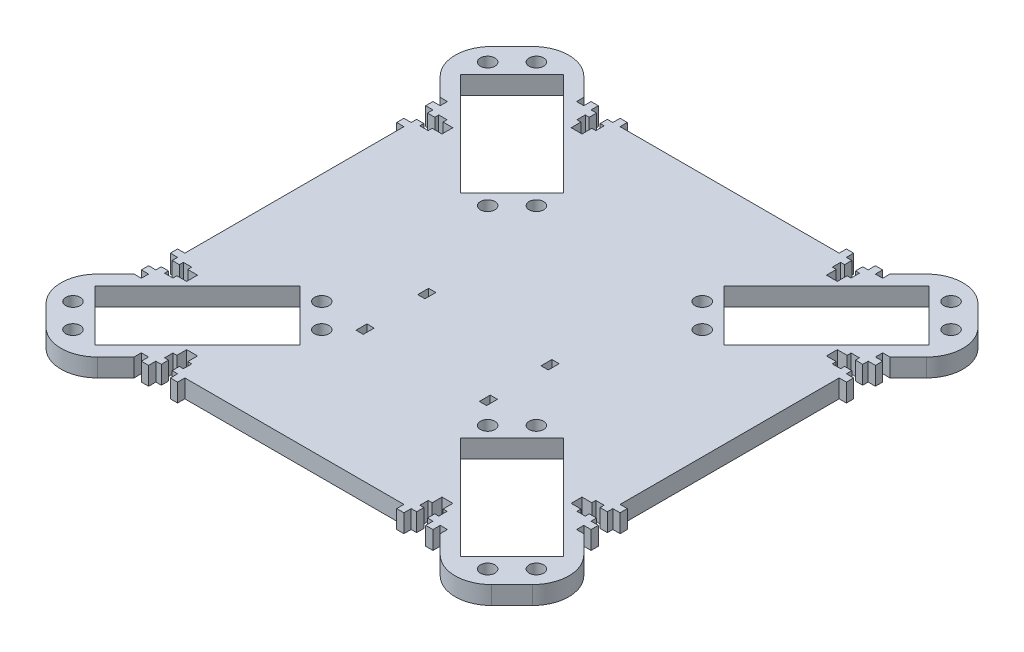
SolidWorks part; units mm, degrees
ref_plane "Front Plane" through (0, 0, 0) normal (0, 0, 1) x (1, 0, 0)
ref_plane "Top Plane" through (0, 0, 0) normal (0, 1, 0) x (1, 0, 0)
ref_plane "Right Plane" through (0, 0, 0) normal (1, 0, 0) x (0, 0, -1)
sketch "Sketch1" plane through (0, 0, 0) normal (0, 1, 0) x (1, 0, 0)
  line L1 (0, 0) -> (120, 0)
  line L2 (0, 0) -> (0, 120)
  line L3 (0, 120) -> (120, 120)
  line L4 (120, 0) -> (120, 120)
  dimension "D1" = 120
  dimension "D2" = 120
extrude "Boss-Extrude1" add sketch "Sketch1" along normal blind 5
sketch "Sketch2" plane through (0, 5, 0) normal (0, 1, 0) x (1, 0, 0)
  line L0 (60, 120) -> (60, 0) construction
  line L1 (120, 120) -> (0, 120) construction
  line L2 (0, 0) -> (120, 0) construction
  line L3 (120, 60) -> (0, 60) construction
  line L4 (120, 0) -> (120, 120) construction
  line L5 (0, 120) -> (0, 0) construction
  line L6 (60, 60) -> (120, 120) construction
  line L7 (110.1005, 110.1005) -> (120, 100.201) construction
  line L8 (110.1005, 110.1005) -> (100.201, 120) construction
  line L9 (100.201, 120) -> (120, 100.201)
  line L10 (100.201, 120) -> (114.3431, 134.1421)
  line L11 (120, 100.201) -> (134.1421, 114.3431)
  line L12 (114.3431, 134.1421) -> (134.1421, 114.3431)
  line L13 (0, 100.201) -> (-14.1421, 114.3431)
  line L14 (5.6569, 134.1421) -> (-14.1421, 114.3431)
  line L15 (19.799, 120) -> (5.6569, 134.1421)
  line L16 (19.799, 120) -> (0, 100.201)
  line L17 (19.799, 0) -> (0, 19.799)
  line L18 (19.799, 0) -> (5.6569, -14.1421)
  line L19 (5.6569, -14.1421) -> (-14.1421, 5.6569)
  line L20 (0, 19.799) -> (-14.1421, 5.6569)
  line L21 (120, 19.799) -> (134.1421, 5.6569)
  line L22 (114.3431, -14.1421) -> (134.1421, 5.6569)
  line L23 (100.201, 0) -> (114.3431, -14.1421)
  line L24 (100.201, 0) -> (120, 19.799)
  point P33 (120, 100.201)
  point P34 (100.201, 120)
  dimension "D1" = 28
  dimension "D2" = 20
extrude "Boss-Extrude3" add sketch "Sketch2" against normal blind 5
sketch "Sketch3" plane through (0, 5, 0) normal (0, 1, 0) x (1, 0, 0)
  line L0 (-4.2426, -4.2426) -> (124.2426, 124.2426) construction
  line L1 (-14.1421, 5.6569) -> (5.6569, -14.1421) construction
  line L2 (134.1421, 114.3431) -> (114.3431, 134.1421) construction
  line L3 (0, 19.799) -> (19.799, 0) construction
  line L4 (2.4819, 2.4819) -> (12.3814, -7.4176) construction
  line L5 (5.6569, -14.1421) -> (19.799, 0) construction
  line L6 (30.7662, 30.7662) -> (43.5292, 18.0033) construction
  line L7 (9.553, -4.5891) -> (37.8373, 23.6951)
  line L8 (9.553, -4.5891) -> (-4.5891, 9.553)
  line L9 (37.8373, 23.6951) -> (23.6951, 37.8373)
  line L10 (-4.5891, 9.553) -> (23.6951, 37.8373)
  line L11 (-0.5233, -0.5233) -> (6.5401, -7.5867) construction
  line L12 (23.6951, 9.553) -> (9.553, 23.6951) construction
  line L13 (0, 60) -> (120, 60) construction
  line L14 (0, 100.201) -> (0, 19.799) construction
  line L15 (120, 19.799) -> (120, 100.201) construction
  line L16 (60, 0) -> (60, 120) construction
  line L17 (19.799, 0) -> (100.201, 0) construction
  line L18 (100.201, 120) -> (19.799, 120) construction
  line L19 (82.1627, 23.6951) -> (96.3049, 37.8373)
  line L20 (124.5891, 9.553) -> (96.3049, 37.8373)
  line L21 (110.447, -4.5891) -> (124.5891, 9.553)
  line L22 (110.447, -4.5891) -> (82.1627, 23.6951)
  line L23 (110.447, 124.5891) -> (82.1627, 96.3049)
  line L24 (110.447, 124.5891) -> (124.5891, 110.447)
  line L25 (124.5891, 110.447) -> (96.3049, 82.1627)
  line L26 (82.1627, 96.3049) -> (96.3049, 82.1627)
  line L27 (37.8373, 96.3049) -> (23.6951, 82.1627)
  line L28 (-4.5891, 110.447) -> (23.6951, 82.1627)
  line L29 (9.553, 124.5891) -> (-4.5891, 110.447)
  line L30 (9.553, 124.5891) -> (37.8373, 96.3049)
  circle A0 centre (2.8355, -3.882) radius 2
  circle A1 centre (-3.882, 2.8355) radius 2
  circle A2 centre (37.1302, 30.4127) radius 2
  circle A3 centre (30.4127, 37.1302) radius 2
  circle A4 centre (117.1645, -3.882) radius 2
  circle A5 centre (123.882, 2.8355) radius 2
  circle A6 centre (82.8698, 30.4127) radius 2
  circle A7 centre (89.5873, 37.1302) radius 2
  circle A8 centre (117.1645, 123.882) radius 2
  circle A9 centre (123.882, 117.1645) radius 2
  circle A10 centre (82.8698, 89.5873) radius 2
  circle A11 centre (89.5873, 82.8698) radius 2
  circle A12 centre (2.8355, 123.882) radius 2
  circle A13 centre (-3.882, 117.1645) radius 2
  circle A14 centre (37.1302, 89.5873) radius 2
  circle A15 centre (30.4127, 82.8698) radius 2
  point P10 (9.8995, 9.8995)
  point P11 (30.7662, 30.7662)
  point P13 (2.4819, 2.4819)
  dimension "D5" = 4
  dimension "D6" = 9.5
  dimension "D7" = 4.25
  dimension "D1" = 29.51
  dimension "D2" = 10.49
  dimension "D3" = 20
  dimension "D4" = 4.25
extrude "Cut-Extrude1" cut sketch "Sketch3" against normal blind 5
sketch "Sketch6" plane through (0, 5, 0) normal (0, 1, 0) x (1, 0, 0)
  line L0 (0, 19.799) -> (0, 17.799)
  line L1 (0, 17.799) -> (-2, 17.799)
  line L2 (0, 19.799) -> (-14.1421, 5.6569) construction
  line L3 (-2, 17.799) -> (0, 19.799)
  line L4 (0, 0) -> (124.2426, 124.2426) construction
  line L5 (134.1421, 114.3431) -> (114.3431, 134.1421) construction
  line L6 (60, 120) -> (60, 0) construction
  line L7 (100.201, 120) -> (19.799, 120) construction
  line L8 (19.799, 0) -> (100.201, 0) construction
  line L9 (0, 60) -> (120, 60) construction
  line L10 (0, 100.201) -> (0, 19.799) construction
  line L11 (120, 19.799) -> (120, 100.201) construction
  line L12 (17.799, -2) -> (19.799, 0)
  line L13 (17.799, 0) -> (17.799, -2)
  line L14 (19.799, 0) -> (17.799, 0)
  line L15 (100.201, 0) -> (102.201, 0)
  line L16 (102.201, 0) -> (102.201, -2)
  line L17 (102.201, -2) -> (100.201, 0)
  line L18 (122, 17.799) -> (120, 19.799)
  line L19 (120, 17.799) -> (122, 17.799)
  line L20 (120, 19.799) -> (120, 17.799)
  line L21 (120, 100.201) -> (120, 102.201)
  line L22 (120, 102.201) -> (122, 102.201)
  line L23 (122, 102.201) -> (120, 100.201)
  line L24 (102.201, 122) -> (100.201, 120)
  line L25 (102.201, 120) -> (102.201, 122)
  line L26 (100.201, 120) -> (102.201, 120)
  line L27 (19.799, 120) -> (17.799, 120)
  line L28 (17.799, 120) -> (17.799, 122)
  line L29 (17.799, 122) -> (19.799, 120)
  line L30 (-2, 102.201) -> (0, 100.201)
  line L31 (0, 102.201) -> (-2, 102.201)
  line L32 (0, 100.201) -> (0, 102.201)
  dimension "D1" = 2
extrude "Cut-Extrude4" cut sketch "Sketch6" against normal blind 10
fillet "Fillet1" radius 10 8 edges at (5.6569, 2.5, 14.1421) (-14.1421, 2.5, -5.6569) (-14.1421, 2.5, -114.3431) (5.6569, 2.5, -134.1421) (114.3431, 2.5, -134.1421) (134.1421, 2.5, -114.3431) (134.1421, 2.5, -5.6569) (114.3431, 2.5, 14.1421)
sketch "Sketch8" plane through (0, 5, 0) normal (0, 1, 0) x (1, 0, 0)
  line L0 (60, 0) -> (60, 120) construction
  line L1 (17.799, 0) -> (102.201, 0) construction
  line L2 (102.201, 120) -> (17.799, 120) construction
  line L3 (0, 60) -> (120, 60) construction
  line L4 (0, 102.201) -> (0, 17.799) construction
  line L5 (120, 17.799) -> (120, 102.201) construction
  line L6 (-4.2426, 124.2426) -> (124.2426, -4.2426) construction
  line L7 (-1.4142, 127.0711) -> (-7.0711, 121.4142) construction
  line L8 (121.4142, -7.0711) -> (127.0711, -1.4142) construction
  line L9 (24.799, 0) -> (24.799, 7) construction
  line L10 (23.299, 2) -> (23.299, 0)
  line L11 (26.299, 7) -> (23.299, 7)
  line L12 (26.299, 7) -> (26.299, 4.3)
  line L13 (26.299, 0) -> (23.299, 0)
  line L14 (23.299, 7) -> (23.299, 4.3)
  line L15 (26.299, 7) -> (23.299, 0) construction
  line L16 (26.299, 0) -> (23.299, 7) construction
  line L17 (23.299, 2) -> (22.199, 2)
  line L19 (23.299, 4.3) -> (22.199, 4.3)
  line L20 (22.199, 2) -> (22.199, 4.3)
  line L21 (26.299, 4.3) -> (27.399, 4.3)
  line L22 (27.399, 2) -> (27.399, 4.3)
  line L23 (26.299, 2) -> (27.399, 2)
  line L24 (26.299, 2) -> (26.299, 0)
  line L25 (17.799, 0) -> (17.799, -2) construction
  line L26 (93.701, 0) -> (96.701, 7) construction
  line L27 (93.701, 7) -> (96.701, 0) construction
  line L28 (95.201, 0) -> (95.201, 7) construction
  line L29 (93.701, 2) -> (93.701, 0)
  line L30 (93.701, 2) -> (92.601, 2)
  line L31 (92.601, 2) -> (92.601, 4.3)
  line L32 (93.701, 4.3) -> (92.601, 4.3)
  line L33 (97.801, 2) -> (97.801, 4.3)
  line L34 (96.701, 4.3) -> (97.801, 4.3)
  line L35 (96.701, 2) -> (97.801, 2)
  line L36 (96.701, 7) -> (96.701, 4.3)
  line L37 (93.701, 0) -> (96.701, 0)
  line L38 (93.701, 7) -> (93.701, 4.3)
  line L39 (93.701, 7) -> (96.701, 7)
  line L40 (96.701, 2) -> (96.701, 0)
  line L41 (95.201, 120) -> (95.201, 113) construction
  line L42 (93.701, 113) -> (96.701, 120) construction
  line L43 (93.701, 120) -> (96.701, 113) construction
  line L44 (26.299, 120) -> (23.299, 113) construction
  line L45 (26.299, 113) -> (23.299, 120) construction
  line L46 (24.799, 120) -> (24.799, 113) construction
  line L47 (96.701, 118) -> (96.701, 120)
  line L48 (93.701, 113) -> (96.701, 113)
  line L49 (93.701, 113) -> (93.701, 115.7)
  line L50 (93.701, 120) -> (96.701, 120)
  line L51 (96.701, 113) -> (96.701, 115.7)
  line L52 (96.701, 118) -> (97.801, 118)
  line L53 (96.701, 115.7) -> (97.801, 115.7)
  line L54 (97.801, 118) -> (97.801, 115.7)
  line L55 (93.701, 115.7) -> (92.601, 115.7)
  line L56 (92.601, 118) -> (92.601, 115.7)
  line L57 (93.701, 118) -> (92.601, 118)
  line L58 (93.701, 118) -> (93.701, 120)
  line L59 (26.299, 118) -> (26.299, 120)
  line L60 (26.299, 118) -> (27.399, 118)
  line L61 (27.399, 118) -> (27.399, 115.7)
  line L62 (26.299, 115.7) -> (27.399, 115.7)
  line L63 (22.199, 118) -> (22.199, 115.7)
  line L64 (23.299, 115.7) -> (22.199, 115.7)
  line L65 (23.299, 118) -> (22.199, 118)
  line L66 (23.299, 113) -> (23.299, 115.7)
  line L67 (26.299, 120) -> (23.299, 120)
  line L68 (26.299, 113) -> (26.299, 115.7)
  line L69 (26.299, 113) -> (23.299, 113)
  line L70 (23.299, 118) -> (23.299, 120)
  line L71 (0, 95.201) -> (7, 95.201) construction
  line L72 (7, 93.701) -> (0, 96.701) construction
  line L73 (0, 93.701) -> (7, 96.701) construction
  line L74 (0, 26.299) -> (7, 23.299) construction
  line L75 (7, 26.299) -> (0, 23.299) construction
  line L76 (0, 24.799) -> (7, 24.799) construction
  line L77 (120, 24.799) -> (113, 24.799) construction
  line L78 (113, 26.299) -> (120, 23.299) construction
  line L79 (120, 26.299) -> (113, 23.299) construction
  line L80 (120, 93.701) -> (113, 96.701) construction
  line L81 (113, 93.701) -> (120, 96.701) construction
  line L82 (120, 95.201) -> (113, 95.201) construction
  line L83 (2, 96.701) -> (0, 96.701)
  line L84 (7, 93.701) -> (7, 96.701)
  line L85 (7, 93.701) -> (4.3, 93.701)
  line L86 (0, 93.701) -> (0, 96.701)
  line L87 (7, 96.701) -> (4.3, 96.701)
  line L88 (2, 96.701) -> (2, 97.801)
  line L89 (4.3, 96.701) -> (4.3, 97.801)
  line L90 (2, 97.801) -> (4.3, 97.801)
  line L91 (4.3, 93.701) -> (4.3, 92.601)
  line L92 (2, 92.601) -> (4.3, 92.601)
  line L93 (2, 93.701) -> (2, 92.601)
  line L94 (2, 93.701) -> (0, 93.701)
  line L95 (2, 26.299) -> (0, 26.299)
  line L96 (2, 26.299) -> (2, 27.399)
  line L97 (2, 27.399) -> (4.3, 27.399)
  line L98 (4.3, 26.299) -> (4.3, 27.399)
  line L99 (2, 22.199) -> (4.3, 22.199)
  line L100 (4.3, 23.299) -> (4.3, 22.199)
  line L101 (2, 23.299) -> (2, 22.199)
  line L102 (7, 23.299) -> (4.3, 23.299)
  line L103 (0, 26.299) -> (0, 23.299)
  line L104 (7, 26.299) -> (4.3, 26.299)
  line L105 (7, 26.299) -> (7, 23.299)
  line L106 (2, 23.299) -> (0, 23.299)
  line L107 (118, 23.299) -> (120, 23.299)
  line L108 (113, 26.299) -> (113, 23.299)
  line L109 (113, 26.299) -> (115.7, 26.299)
  line L110 (120, 26.299) -> (120, 23.299)
  line L111 (113, 23.299) -> (115.7, 23.299)
  line L112 (118, 23.299) -> (118, 22.199)
  line L113 (115.7, 23.299) -> (115.7, 22.199)
  line L114 (118, 22.199) -> (115.7, 22.199)
  line L115 (115.7, 26.299) -> (115.7, 27.399)
  line L116 (118, 27.399) -> (115.7, 27.399)
  line L117 (118, 26.299) -> (118, 27.399)
  line L118 (118, 26.299) -> (120, 26.299)
  line L119 (118, 93.701) -> (120, 93.701)
  line L120 (118, 93.701) -> (118, 92.601)
  line L121 (118, 92.601) -> (115.7, 92.601)
  line L122 (115.7, 93.701) -> (115.7, 92.601)
  line L123 (118, 97.801) -> (115.7, 97.801)
  line L124 (115.7, 96.701) -> (115.7, 97.801)
  line L125 (118, 96.701) -> (118, 97.801)
  line L126 (113, 96.701) -> (115.7, 96.701)
  line L127 (120, 93.701) -> (120, 96.701)
  line L128 (113, 93.701) -> (115.7, 93.701)
  line L129 (113, 93.701) -> (113, 96.701)
  line L130 (118, 96.701) -> (120, 96.701)
  point P20 (24.799, 3.5)
  point P49 (95.201, 3.5)
  point P78 (95.201, 116.5)
  point P79 (24.799, 116.5)
  point P136 (3.5, 95.201)
  point P137 (3.5, 24.799)
  point P138 (116.5, 24.799)
  point P139 (116.5, 95.201)
  dimension "D1" = 2
  dimension "D2" = 2.3
  dimension "D3" = 7
  dimension "D4" = 7
  dimension "D5" = 3
  dimension "D6" = 1.1
extrude "Cut-Extrude6" cut sketch "Sketch8" against normal blind 10
sketch "Sketch9" plane through (0, 5, 0) normal (0, 1, 0) x (1, 0, 0)
  line L0 (7, 95.201) -> (-3.557, 95.201) construction
  line L1 (7, 93.701) -> (7, 96.701) construction
  line L2 (-4.2426, 124.2426) -> (124.2426, -4.2426) construction
  line L3 (-1.4142, 127.0711) -> (-7.0711, 121.4142) construction
  line L4 (121.4142, -7.0711) -> (127.0711, -1.4142) construction
  line L5 (60, 0) -> (60, 120) construction
  line L6 (26.299, 0) -> (93.701, 0) construction
  line L7 (93.701, 120) -> (26.299, 120) construction
  line L8 (0, 60) -> (120, 60) construction
  line L9 (0, 93.701) -> (0, 26.299) construction
  line L10 (120, 26.299) -> (120, 93.701) construction
  line L11 (0, 102.201) -> (0, 96.701) construction
  line L12 (0, 98.201) -> (-2, 98.201)
  line L13 (0, 98.201) -> (0, 100.201)
  line L14 (0, 100.201) -> (-2, 100.201)
  line L15 (-2, 98.201) -> (-2, 100.201)
  line L16 (0, 90.201) -> (-2, 90.201)
  line L17 (-2, 92.201) -> (-2, 90.201)
  line L18 (0, 92.201) -> (-2, 92.201)
  line L19 (0, 92.201) -> (0, 90.201)
  line L20 (19.799, 120) -> (19.799, 122)
  line L21 (21.799, 122) -> (19.799, 122)
  line L22 (21.799, 120) -> (21.799, 122)
  line L23 (21.799, 120) -> (19.799, 120)
  line L24 (27.799, 120) -> (29.799, 120)
  line L25 (27.799, 120) -> (27.799, 122)
  line L26 (27.799, 122) -> (29.799, 122)
  line L27 (29.799, 120) -> (29.799, 122)
  line L28 (92.201, 120) -> (92.201, 122)
  line L29 (92.201, 122) -> (90.201, 122)
  line L30 (90.201, 120) -> (90.201, 122)
  line L31 (92.201, 120) -> (90.201, 120)
  line L32 (98.201, 120) -> (100.201, 120)
  line L33 (98.201, 120) -> (98.201, 122)
  line L34 (98.201, 122) -> (100.201, 122)
  line L35 (100.201, 120) -> (100.201, 122)
  line L36 (120, 100.201) -> (122, 100.201)
  line L37 (122, 98.201) -> (122, 100.201)
  line L38 (120, 98.201) -> (122, 98.201)
  line L39 (120, 98.201) -> (120, 100.201)
  line L40 (120, 92.201) -> (120, 90.201)
  line L41 (120, 92.201) -> (122, 92.201)
  line L42 (122, 92.201) -> (122, 90.201)
  line L43 (120, 90.201) -> (122, 90.201)
  line L44 (120, 27.799) -> (122, 27.799)
  line L45 (122, 27.799) -> (122, 29.799)
  line L46 (120, 29.799) -> (122, 29.799)
  line L47 (120, 27.799) -> (120, 29.799)
  line L48 (120, 21.799) -> (120, 19.799)
  line L49 (120, 21.799) -> (122, 21.799)
  line L50 (122, 21.799) -> (122, 19.799)
  line L51 (120, 19.799) -> (122, 19.799)
  line L52 (98.201, 0) -> (98.201, -2)
  line L53 (98.201, -2) -> (100.201, -2)
  line L54 (100.201, 0) -> (100.201, -2)
  line L55 (98.201, 0) -> (100.201, 0)
  line L56 (92.201, 0) -> (90.201, 0)
  line L57 (90.201, 0) -> (90.201, -2)
  line L58 (92.201, -2) -> (90.201, -2)
  line L59 (92.201, 0) -> (92.201, -2)
  line L60 (27.799, 0) -> (27.799, -2)
  line L61 (27.799, -2) -> (29.799, -2)
  line L62 (29.799, 0) -> (29.799, -2)
  line L63 (27.799, 0) -> (29.799, 0)
  line L64 (21.799, 0) -> (19.799, 0)
  line L65 (21.799, 0) -> (21.799, -2)
  line L66 (21.799, -2) -> (19.799, -2)
  line L67 (19.799, 0) -> (19.799, -2)
  line L68 (0, 19.799) -> (-2, 19.799)
  line L69 (-2, 21.799) -> (-2, 19.799)
  line L70 (0, 21.799) -> (-2, 21.799)
  line L71 (0, 21.799) -> (0, 19.799)
  line L72 (0, 27.799) -> (0, 29.799)
  line L73 (0, 27.799) -> (-2, 27.799)
  line L74 (-2, 27.799) -> (-2, 29.799)
  line L75 (0, 29.799) -> (-2, 29.799)
  dimension "D1" = 2
  dimension "D2" = 2
  dimension "D3" = 3
extrude "Boss-Extrude4" add sketch "Sketch9" against normal blind 5
sketch "Sketch10" plane through (0, 5, 0) normal (0, 1, 0) x (1, 0, 0)
  line L0 (60, 123.9005) -> (60, 0) construction
  line L1 (60, 68) -> (70, 68) construction
  line L10 (60, 28) -> (76, 28) construction
  line L11 (76, 28) -> (76, 52) construction
  line L12 (76, 45) -> (60, 45) construction
  line L13 (76, 52) -> (78, 52)
  line L14 (76, 52) -> (76, 55)
  line L15 (76, 55) -> (78, 55)
  line L16 (78, 52) -> (78, 55)
  line L17 (76, 35) -> (78, 35)
  line L18 (78, 38) -> (78, 35)
  line L19 (76, 38) -> (78, 38)
  line L20 (76, 38) -> (76, 35)
  line L21 (44, 38) -> (44, 35)
  line L22 (44, 38) -> (42, 38)
  line L23 (42, 38) -> (42, 35)
  line L24 (44, 35) -> (42, 35)
  line L25 (44, 55) -> (42, 55)
  line L26 (42, 52) -> (42, 55)
  line L27 (44, 52) -> (42, 52)
  line L28 (44, 52) -> (44, 55)
  line L29 (29.799, 0) -> (90.201, 0) construction
  point P34 (60, 0)
  dimension "D1" = 3
  dimension "D2" = 2
  dimension "D5" = 10
  dimension "D6" = 17
  dimension "D7" = 16
extrude "Cut-Extrude7" cut sketch "Sketch10" against normal blind 10
